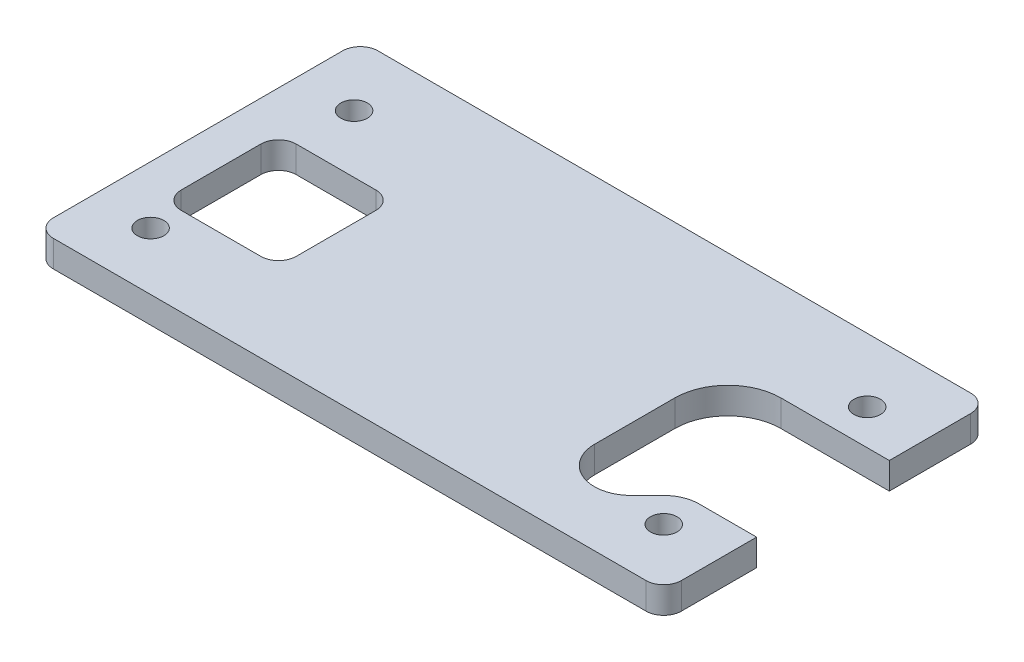
SolidWorks part; units mm, degrees
ref_plane "Front Plane" through (0, 0, 0) normal (0, 0, 1) x (1, 0, 0)
ref_plane "Top Plane" through (0, 0, 0) normal (0, 1, 0) x (1, 0, 0)
ref_plane "Right Plane" through (0, 0, 0) normal (1, 0, 0) x (0, 0, -1)
sketch "Sketch1" plane through (0, 0, 0) normal (0, 1, 0) x (1, 0, 0)
  line L0 (-35.5, 18.35) -> (35.5, 18.35)
  line L1 (-32.5, -15.35) -> (32.5, -15.35) construction
  line L2 (-32.5, -15.35) -> (-32.5, 15.35) construction
  line L3 (-32.5, 15.35) -> (32.5, 15.35) construction
  line L4 (32.5, -15.35) -> (32.5, 15.35) construction
  line L5 (0, 15.35) -> (0, -15.35) construction
  line L6 (-32.5, 0) -> (32.5, 0) construction
  line L11 (35.5, -18.35) -> (35.5, 18.35)
  line L12 (-35.5, -18.35) -> (35.5, -18.35)
  line L13 (-35.5, -18.35) -> (-35.5, 18.35)
  line L15 (-29, -11.85) -> (29, -11.85) construction
  line L16 (-29, -11.85) -> (-29, 11.15) construction
  line L17 (-29, 11.15) -> (29, 11.15) construction
  line L18 (29, -11.85) -> (29, 11.15) construction
  line L19 (0, 11.15) -> (0, -11.85) construction
  line L20 (-29, -0.35) -> (29, -0.35) construction
  circle A0 centre (-29, -11.85) radius 1.5
  circle A1 centre (29, -11.85) radius 1.5
  circle A2 centre (29, 11.15) radius 1.5
  circle A3 centre (-29, 11.15) radius 1.5
  point P0 (0, 0)
  point P8 (0, -0.35)
  point P16 (0, 0)
  point P17 (-29, -11.2325)
  dimension "D4" = 3
  dimension "D1" = 65
  dimension "D2" = 30.7
  dimension "D5" = 3.5
  dimension "D6" = 4.2
  dimension "D7" = 3.5
  dimension "D8" = 23
  dimension "D9" = 58
  dimension "D3" = 3
extrude "Boss-Extrude1" add sketch "Sketch1" along normal blind 3
sketch "Sketch2" plane through (0, 3, 0) normal (0, 1, 0) x (1, 0, 0)
  line L0 (-18, -8.39) -> (-31, -8.39)
  line L1 (-19.5, -6.89) -> (-29.5, -6.89) construction
  line L2 (-19.5, -6.89) -> (-19.5, 3.11) construction
  line L3 (-19.5, 3.11) -> (-29.5, 3.11) construction
  line L4 (-29.5, -6.89) -> (-29.5, 3.11) construction
  line L5 (-24.5, 3.11) -> (-24.5, -6.89) construction
  line L6 (-19.5, -1.89) -> (-29.5, -1.89) construction
  line L7 (-31, -8.39) -> (-31, 4.61)
  line L8 (-18, 4.61) -> (-31, 4.61)
  line L9 (-18, -8.39) -> (-18, 4.61)
  line L10 (-32.5, -15.35) -> (32.5, -15.35) construction
  line L11 (-32.5, -15.35) -> (-32.5, 15.35) construction
  line L12 (32.5, -15.35) -> (32.5, 15.35) construction
  line L13 (17.25, 1.15) -> (17.25, -7.9341)
  line L14 (24.3274, -10.8657) -> (26.1716, -9.0216)
  line L15 (29, -7.85) -> (35.5, -7.85)
  line L16 (35.5, -7.85) -> (35.5, 7.15)
  line L17 (35.5, 7.15) -> (23.25, 7.15)
  line L18 (35.5, -18.35) -> (35.5, 18.35) construction
  circle A0 centre (21.25, -6.08) radius 3 construction
  circle A1 centre (28.59, 0.4) radius 3 construction
  circle A2 centre (29, -11.85) radius 4 construction
  circle A3 centre (29, -11.85) radius 1.5 construction
  arc A4 (24.3274, -10.8657) -> (17.25, -7.9341) centre (21.3959, -7.9341) cw
  circle A5 centre (29, 11.15) radius 4 construction
  circle A6 centre (29, 11.15) radius 1.5 construction
  arc A7 (29, -7.85) -> (26.1716, -9.0216) centre (29, -11.85) ccw
  arc A8 (23.25, 7.15) -> (17.25, 1.15) centre (23.25, 1.15) ccw
  point P0 (-24.5, -1.89)
  point P20 (18.25, -6.08)
  point P25 (21.3959, -12.08)
  point P28 (21.25, -9.08)
  dimension "D9" = 6
  dimension "D11" = 8
  dimension "D14" = 6
  dimension "D2" = 10
  dimension "D3" = 13.46
  dimension "D4" = 8
  dimension "D5" = 15.75
  dimension "D6" = 3.91
  dimension "D7" = 11.25
  dimension "D8" = 9.27
  dimension "D10" = 1
  dimension "D12" = 45
  dimension "D13" = 3
  dimension "D1" = 1.5
extrude "Cut-Extrude1" cut sketch "Sketch2" against normal through all
fillet "Fillet1" radius 2 4 edges at (-18, 1.5, 8.39) (-31, 1.5, 8.39) (-18, 1.5, -4.61) (-31, 1.5, -4.61)
fillet "Fillet2" radius 2 4 edges at (35.5, 1.5, -18.35) (35.5, 1.5, 18.35) (-35.5, 1.5, 18.35) (-35.5, 1.5, -18.35)
